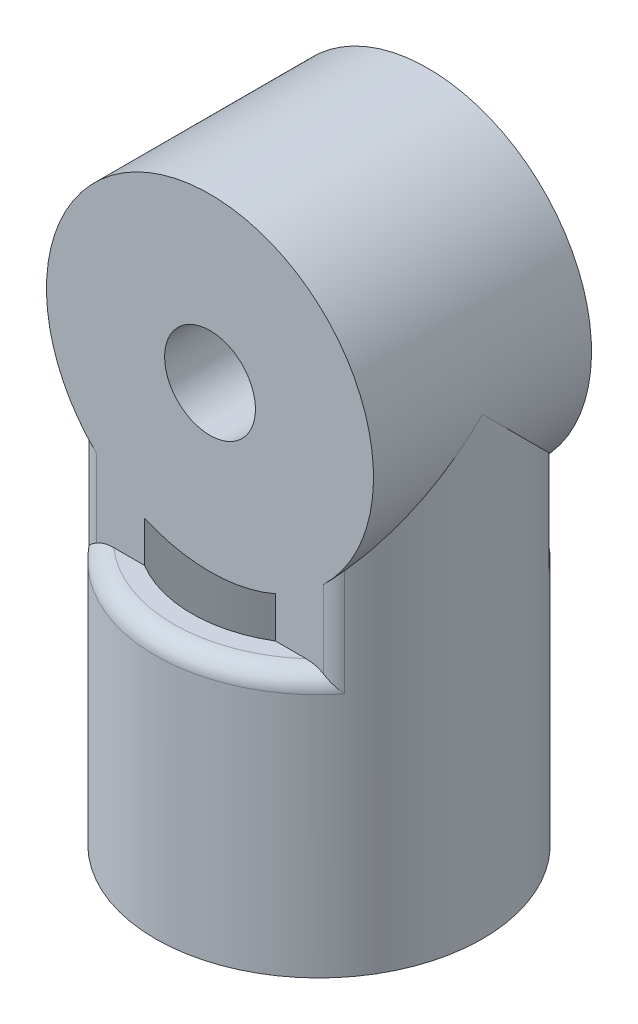
SolidWorks part; units mm, degrees
material "Rubber"
ref_plane "Front Plane" through (0, 0, 0) normal (0, 0, 1) x (1, 0, 0)
ref_plane "Top Plane" through (0, 0, 0) normal (0, 1, 0) x (1, 0, 0)
ref_plane "Right Plane" through (0, 0, 0) normal (1, 0, 0) x (0, 0, -1)
sketch "Sketch1" plane through (0, 0, 0) normal (0, 1, 0) x (1, 0, 0)
  circle A0 centre (0, 0) radius 7
  circle A1 centre (0, 0) radius 9
extrude "Boss-Extrude1" add sketch "Sketch1" along normal blind 25
ref_plane "Plane1" through (0, 0, 9) normal (0, 0, 1) x (1, 0, 0)
sketch "Sketch2" plane through (0, 0, 9) normal (0, 0, 1) x (1, 0, 0)
  line L0 (7, 25) -> (-7, 25) construction
  circle A0 centre (0, 25) radius 9
extrude "Cut-Extrude2" cut sketch "Sketch2" against normal blind 27 and the other way blind 12
sketch "Sketch4" plane through (0, 0, 0) normal (0, 0, 1) x (1, 0, 0)
  circle A0 centre (0, 25) radius 9
extrude "Boss-Extrude8" add sketch "Sketch4" along normal blind 9 and the other way blind 9
sketch "Sketch5" plane through (0, 0, 9) normal (0, 0, 1) x (1, 0, 0)
  circle A0 centre (0, 25) radius 8
extrude "Cut-Extrude3" cut sketch "Sketch5" against normal blind 3
sketch "Sketch6" plane through (0, 0, -9) normal (0, 0, -1) x (-1, 0, 0)
  circle A0 centre (0, 25) radius 8
extrude "Cut-Extrude4" cut sketch "Sketch6" against normal blind 3
sketch "Sketch7" plane through (0, 0, -6) normal (0, 0, -1) x (-1, 0, 0)
  circle A0 centre (0, 25) radius 2.5
extrude "Cut-Extrude5" cut sketch "Sketch7" against normal blind 17
sketch "Sketch8" plane through (0, 0, 6) normal (0, 0, 1) x (1, 0, 0)
  line L0 (-10.5, 25) -> (-10.5, 14.5)
  line L1 (-10.5, 14.5) -> (10.5, 14.5)
  line L2 (10.5, 14.5) -> (10.5, 25)
  arc A0 (10.5, 25) -> (-10.5, 25) centre (0, 25) ccw
extrude "Cut-Extrude6" cut sketch "Sketch8" along normal blind 15
mirror "Mirror1" about plane through (0, 0, 0) normal (0, 0, 1) of "Cut-Extrude6"
fillet "Fillet2" radius 1 6 edges at (0, 14.5, -9) (6.7082, 16.75, -6) (6.7082, 16.75, 6) (-6.7082, 16.75, 6) (-6.7082, 16.75, -6) (0, 14.5, 9)
